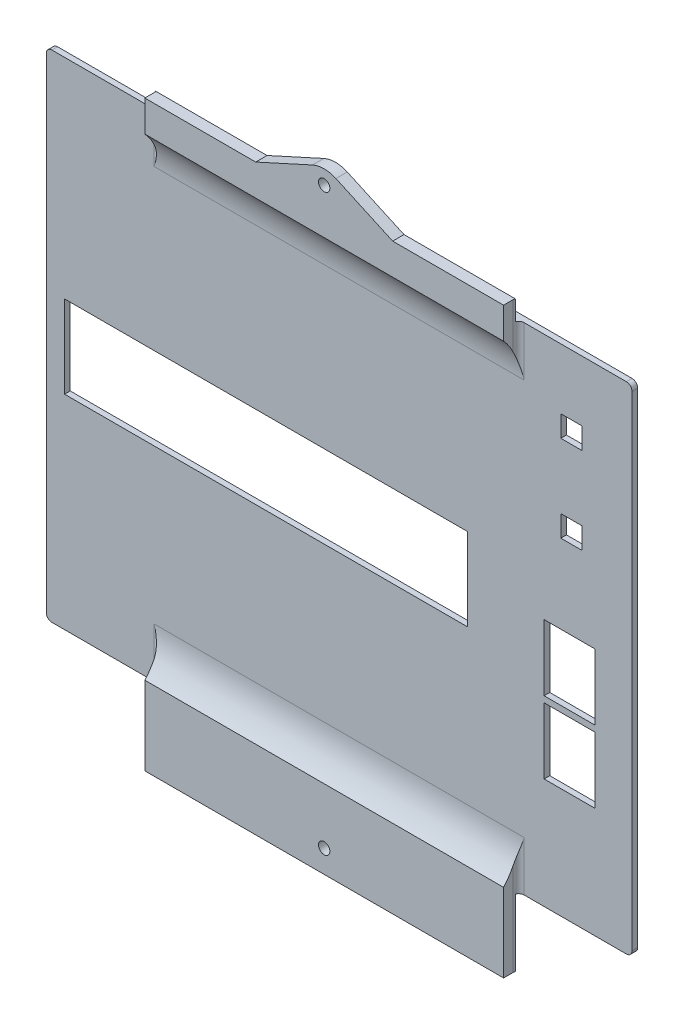
SolidWorks part; units mm, degrees
ref_plane "Front Plane" through (0, 0, 0) normal (0, 0, 1) x (1, 0, 0)
ref_plane "Top Plane" through (0, 0, 0) normal (0, 1, 0) x (1, 0, 0)
ref_plane "Right Plane" through (0, 0, 0) normal (1, 0, 0) x (0, 0, -1)
sketch "ref from switch network" plane through (0, 0, 0) normal (0, 0, 1) x (1, 0, 0)
  line L4 (-129.3534, -65.2777) -> (-25.1184, -65.2777)
  line L5 (-25.1184, -65.2777) -> (-25.1184, 23.0823)
  line L6 (-25.1184, 23.0823) -> (-129.3534, 23.0823)
  line L7 (-129.3534, 23.0823) -> (-129.3534, -65.2777)
  line L8 (-129.3534, -65.2777) -> (-25.1184, -65.2777)
  line L9 (-25.1184, -65.2777) -> (-25.1184, 23.0823)
  line L10 (-25.1184, 23.0823) -> (-129.3534, 23.0823)
  line L11 (-129.3534, 23.0823) -> (-129.3534, -65.2777)
  line L16 (-125.1361, -14.7901) -> (-125.1361, -28.3367) construction
  line L17 (-125.1361, -28.3367) -> (-55.0744, -28.3367) construction
  line L18 (-55.0744, -28.3367) -> (-55.0744, -14.7901) construction
  line L19 (-55.0744, -14.7901) -> (-125.1361, -14.7901) construction
  line L20 (-34.9238, -6.5774) -> (-34.9238, -3.8257) construction
  line L21 (-34.9238, -3.8257) -> (-37.6754, -3.8257) construction
  line L22 (-37.6754, -3.8257) -> (-37.6754, -6.5774) construction
  line L23 (-37.6754, -6.5774) -> (-34.9238, -6.5774) construction
  line L24 (-37.6754, 11.4143) -> (-37.6754, 8.6626) construction
  line L25 (-37.6754, 8.6626) -> (-34.9238, 8.6626) construction
  line L26 (-34.9238, 8.6626) -> (-34.9238, 11.4143) construction
  line L27 (-34.9238, 11.4143) -> (-37.6754, 11.4143) construction
  line L36 (-125.1361, -14.7901) -> (-125.1361, -28.3367)
  line L37 (-125.1361, -28.3367) -> (-55.0744, -28.3367)
  line L38 (-55.0744, -28.3367) -> (-55.0744, -14.7901)
  line L39 (-55.0744, -14.7901) -> (-125.1361, -14.7901)
  line L40 (-34.9238, -6.5774) -> (-34.9238, -3.8257)
  line L41 (-34.9238, -3.8257) -> (-37.6754, -3.8257)
  line L42 (-37.6754, -3.8257) -> (-37.6754, -6.5774)
  line L43 (-37.6754, -6.5774) -> (-34.9238, -6.5774)
  line L44 (-37.6754, 11.4143) -> (-37.6754, 8.6626)
  line L45 (-37.6754, 8.6626) -> (-34.9238, 8.6626)
  line L46 (-34.9238, 8.6626) -> (-34.9238, 11.4143)
  line L47 (-34.9238, 11.4143) -> (-37.6754, 11.4143)
  line L48 (-129.3534, 26.0823) -> (-89.307, 26.0823) construction
  line L49 (-22.5284, -76.6174) -> (-129.3534, -76.6174) construction
  line L50 (-132.3534, -73.6174) -> (-132.3534, 23.0823) construction
  line L51 (-129.3534, 26.0823) -> (-89.307, 26.0823)
  line L52 (-22.5284, -76.6174) -> (-129.3534, -76.6174)
  line L53 (-132.3534, -73.6174) -> (-132.3534, 23.0823)
  line L58 (-40.6184, -21.4787) -> (-40.6184, -32.1044) construction
  line L59 (-40.6184, -32.1044) -> (-32.6184, -32.1044) construction
  line L60 (-32.6184, -32.1044) -> (-32.6184, -21.4787) construction
  line L61 (-32.6184, -21.4787) -> (-40.6184, -21.4787) construction
  line L62 (-32.6184, -34.1787) -> (-40.6184, -34.1787) construction
  line L63 (-40.6184, -34.1787) -> (-40.6184, -44.8044) construction
  line L64 (-40.6184, -44.8044) -> (-32.6184, -44.8044) construction
  line L65 (-32.6184, -44.8044) -> (-32.6184, -34.1787) construction
  line L66 (-40.6184, -21.4787) -> (-40.6184, -32.1044)
  line L67 (-40.6184, -32.1044) -> (-32.6184, -32.1044)
  line L68 (-32.6184, -32.1044) -> (-32.6184, -21.4787)
  line L69 (-32.6184, -21.4787) -> (-40.6184, -21.4787)
  line L70 (-32.6184, -34.1787) -> (-40.6184, -34.1787)
  line L71 (-40.6184, -34.1787) -> (-40.6184, -44.8044)
  line L72 (-40.6184, -44.8044) -> (-32.6184, -44.8044)
  line L73 (-32.6184, -44.8044) -> (-32.6184, -34.1787)
  arc A0 (-129.3534, 26.0823) -> (-132.3534, 23.0823) centre (-129.3534, 23.0823) ccw construction
  arc A1 (-129.3534, 26.0823) -> (-132.3534, 23.0823) centre (-129.3534, 23.0823) ccw
  arc A2 (-132.3534, -73.6174) -> (-129.3534, -76.6174) centre (-129.3534, -73.6174) ccw construction
  arc A3 (-132.3534, -73.6174) -> (-129.3534, -76.6174) centre (-129.3534, -73.6174) ccw
  dimension "D1" = 0
sketch "Sketch2" plane through (0, 0, 0) normal (0, 0, 1) x (1, 0, 0)
  line L8 (-41.1184, -33.6787) -> (-41.1184, -45.3044)
  line L9 (-32.1184, -33.6787) -> (-41.1184, -33.6787)
  line L10 (-32.1184, -45.3044) -> (-32.1184, -33.6787)
  line L11 (-41.1184, -45.3044) -> (-32.1184, -45.3044)
  line L12 (-41.1184, -33.6787) -> (-41.1184, -45.3044)
  line L13 (-32.1184, -33.6787) -> (-41.1184, -33.6787)
  line L14 (-32.1184, -45.3044) -> (-32.1184, -33.6787)
  line L15 (-41.1184, -45.3044) -> (-32.1184, -45.3044)
  line L20 (-41.1184, -20.9787) -> (-41.1184, -32.6044)
  line L21 (-32.1184, -20.9787) -> (-41.1184, -20.9787)
  line L22 (-32.1184, -32.6044) -> (-32.1184, -20.9787)
  line L23 (-41.1184, -32.6044) -> (-32.1184, -32.6044)
  line L24 (-41.1184, -20.9787) -> (-41.1184, -32.6044)
  line L25 (-32.1184, -20.9787) -> (-41.1184, -20.9787)
  line L26 (-32.1184, -32.6044) -> (-32.1184, -20.9787)
  line L27 (-41.1184, -32.6044) -> (-32.1184, -32.6044)
  line L32 (-38.1754, -3.3257) -> (-38.1754, -7.0774)
  line L33 (-34.4238, -3.3257) -> (-38.1754, -3.3257)
  line L34 (-34.4238, -7.0774) -> (-34.4238, -3.3257)
  line L35 (-38.1754, -7.0774) -> (-34.4238, -7.0774)
  line L36 (-38.1754, -3.3257) -> (-38.1754, -7.0774)
  line L37 (-34.4238, -3.3257) -> (-38.1754, -3.3257)
  line L38 (-34.4238, -7.0774) -> (-34.4238, -3.3257)
  line L39 (-38.1754, -7.0774) -> (-34.4238, -7.0774)
  line L44 (-38.1754, 8.1626) -> (-34.4238, 8.1626)
  line L45 (-38.1754, 11.9143) -> (-38.1754, 8.1626)
  line L46 (-34.4238, 11.9143) -> (-38.1754, 11.9143)
  line L47 (-34.4238, 8.1626) -> (-34.4238, 11.9143)
  line L48 (-38.1754, 8.1626) -> (-34.4238, 8.1626)
  line L49 (-38.1754, 11.9143) -> (-38.1754, 8.1626)
  line L50 (-34.4238, 11.9143) -> (-38.1754, 11.9143)
  line L51 (-34.4238, 8.1626) -> (-34.4238, 11.9143)
  line L56 (-54.5744, -28.8367) -> (-54.5744, -14.2901)
  line L57 (-125.6361, -28.8367) -> (-54.5744, -28.8367)
  line L58 (-125.6361, -14.2901) -> (-125.6361, -28.8367)
  line L59 (-54.5744, -14.2901) -> (-125.6361, -14.2901)
  line L60 (-54.5744, -28.8367) -> (-54.5744, -14.2901)
  line L61 (-125.6361, -28.8367) -> (-54.5744, -28.8367)
  line L62 (-125.6361, -14.2901) -> (-125.6361, -28.8367)
  line L63 (-54.5744, -14.2901) -> (-125.6361, -14.2901)
  line L68 (-25.6184, 22.5823) -> (-128.8534, 22.5823)
  line L69 (-25.6184, -64.7777) -> (-25.6184, 22.5823)
  line L70 (-128.8534, -64.7777) -> (-25.6184, -64.7777)
  line L71 (-128.8534, 22.5823) -> (-128.8534, -64.7777)
  line L72 (-25.6184, 22.5823) -> (-128.8534, 22.5823)
  line L73 (-25.6184, -64.7777) -> (-25.6184, 22.5823)
  line L74 (-128.8534, -64.7777) -> (-25.6184, -64.7777)
  line L75 (-128.8534, 22.5823) -> (-128.8534, -64.7777)
  dimension "D1" = 0.5
  dimension "D2" = 0.5
  dimension "D3" = 0.5
  dimension "D4" = 0.5
  dimension "D5" = 0.5
  dimension "D6" = 0.5
extrude "Boss-Extrude1" add sketch "Sketch2" along normal blind 1
sketch "Sketch4" plane through (-128.8534, 0, 0) normal (-1, 0, 0) x (0, 0, 1)
  line L0 (1.44, 23.0823) -> (1.44, 26.0823) construction
  line L1 (1.44, 23.0823) -> (1.44, 26.0823) construction
  line L2 (1.44, -76.6174) -> (1.44, -73.6174) construction
  line L3 (1.44, -76.6174) -> (1.44, -73.6174) construction
  line L4 (1.64, 23.0823) -> (1.64, 26.0823)
  line L5 (1.64, 23.0823) -> (1.64, 22.5823)
  line L6 (1.64, 22.5823) -> (1, 22.5823)
  line L7 (1, 22.5823) -> (1, 20.5823)
  line L8 (1, 22.5823) -> (1, -64.7777) construction
  line L9 (1, 20.5823) -> (3.64, 20.5823)
  line L10 (3.64, 20.5823) -> (3.64, 26.0823)
  line L11 (3.64, 26.0823) -> (1.64, 26.0823)
  line L12 (1.64, -76.6174) -> (1.64, -73.6174)
  line L13 (1.64, -73.6174) -> (1.64, -64.7777)
  line L14 (1, -64.7777) -> (1.64, -64.7777)
  line L15 (1.64, -76.6174) -> (3.64, -76.6174)
  line L16 (3.64, -76.6174) -> (3.64, -62.7777)
  line L17 (3.64, -62.7777) -> (1, -62.7777)
  line L18 (1, -62.7777) -> (1, -64.7777)
  dimension "D2" = 2
  dimension "D3" = 2
  dimension "D5" = 2
  dimension "D6" = 2
  dimension "D1" = 0.2
  dimension "D4" = 0.2
extrude "Boss-Extrude2" add sketch "Sketch4" against normal offset from surface (63.235 mm away) 20 from offset 20 up to face at (-25.6184, -21.0977, 0.5) offset against normal yes
fillet "Fillet1" radius 10 2 edges at (-77.2359, -62.7777, 1) (-77.2359, 20.5823, 1)
fillet "Fillet2" radius 1 4 edges at (-128.8534, 22.5823, 0.5) (-128.8534, -64.7777, 0.5) (-25.6184, -64.7777, 0.5) (-25.6184, 22.5823, 0.5)
fillet "Fillet4" radius 1 4 edges at (-45.6184, -60.3928, 1) (-108.8534, -60.3928, 1)
sketch "Sketch6" plane through (0, 0, 3.64) normal (0, 0, 1) x (1, 0, 0)
  line L0 (-77.2359, 20.5823) -> (-77.2359, 41.487) construction
  line L1 (-45.6184, 20.5823) -> (-108.8534, 20.5823) construction
  line L2 (-45.6184, 26.0823) -> (-108.8534, 26.0823) construction
  line L3 (-89.307, 26.0823) -> (-79.307, 30.6332)
  line L4 (-75.1649, 30.6332) -> (-65.1649, 26.0823)
  line L5 (-89.307, 26.0823) -> (-65.1649, 26.0823)
  arc A0 (-79.307, 30.6332) -> (-75.1649, 30.6332) centre (-77.2359, 26.0823) cw
  dimension "D1" = 5
  dimension "D2" = 10
extrude "Boss-Extrude3" add sketch "Sketch6" against normal up to surface (2 mm away) up to face at (-77.2359, 24.3323, 1.64)
sketch "Sketch5" plane through (0, 0, 3.64) normal (0, 0, 1) x (1, 0, 0)
  line L0 (-77.2359, -76.6174) -> (-77.2359, 28.5823) construction
  line L1 (-45.6184, -76.6174) -> (-108.8534, -76.6174) construction
  line L2 (-89.307, 26.0823) -> (-108.8534, 26.0823) construction
  circle A0 centre (-77.2359, -72.6174) radius 1
  circle A1 centre (-77.2359, 28.5823) radius 1
  dimension "D1" = 2
  dimension "D3" = 2.5
  dimension "D2" = 4
extrude "Cut-Extrude1" cut sketch "Sketch5" against normal through all
sketch "Sketch7" plane through (0, 0, 1) normal (0, 0, 1) x (1, 0, 0)
  line L0 (-126.3878, -7.2961) -> (-48.1432, -7.2961) construction
  line L1 (-126.3878, -48.3456) -> (-48.1432, -48.3456) construction
  text T0 "<b>THE OLD</b>" font "Comic Sans MS" height 7.5
  text T1 "<b><i>SWITCHEROO</i></b>" font "Comic Sans MS" height 8
extrude "Boss-Extrude4" [suppressed] add sketch "Sketch7" along normal blind 2
sketch "Sketch8" [suppressed] plane through (0, 0, 1.64) normal (0, 0, -1) x (-1, 0, 0)
  line L4 (108.9205, -64.7777) -> (45.5514, -64.7777)
  line L5 (45.5514, -64.7777) -> (45.5514, -76.6174)
  line L6 (45.5514, -76.6174) -> (108.9205, -76.6174)
  line L7 (108.9205, -76.6174) -> (108.9205, -64.7777)
  line L8 (108.9205, -64.7777) -> (45.5514, -64.7777)
  line L9 (45.5514, -64.7777) -> (45.5514, -76.6174)
  line L10 (45.5514, -76.6174) -> (108.9205, -76.6174)
  line L11 (108.9205, -76.6174) -> (108.9205, -64.7777)
  line L15 (65.1649, 26.0823) -> (45.5514, 26.0823)
  line L16 (45.5514, 26.0823) -> (45.5514, 22.5823)
  line L17 (45.5514, 22.5823) -> (108.9205, 22.5823)
  line L18 (108.9205, 22.5823) -> (108.9205, 26.0823)
  line L19 (108.9205, 26.0823) -> (89.307, 26.0823)
  line L20 (89.307, 26.0823) -> (79.307, 30.6332)
  line L21 (75.1649, 30.6332) -> (65.1649, 26.0823)
  line L22 (65.1649, 26.0823) -> (45.5514, 26.0823)
  line L23 (45.5514, 26.0823) -> (45.5514, 22.5823)
  line L24 (45.5514, 22.5823) -> (108.9205, 22.5823)
  line L25 (108.9205, 22.5823) -> (108.9205, 26.0823)
  line L26 (108.9205, 26.0823) -> (89.307, 26.0823)
  line L27 (89.307, 26.0823) -> (79.307, 30.6332)
  line L28 (75.1649, 30.6332) -> (65.1649, 26.0823)
  circle A0 centre (77.2359, -72.6174) radius 1 construction
  circle A1 centre (77.2359, -72.6174) radius 1
  circle A2 centre (77.2359, 28.5823) radius 1 construction
  arc A3 (79.307, 30.6332) -> (75.1649, 30.6332) centre (77.2359, 26.0823) ccw
  arc A4 (79.307, 30.6332) -> (75.1649, 30.6332) centre (77.2359, 26.0823) ccw
  circle A5 centre (77.2359, 28.5823) radius 1
  dimension "D1" = 0
  dimension "D2" = 0
extrude "Boss-Extrude5" [suppressed] add sketch "Sketch8" along normal offset from surface (1.44 mm away) 0.2
